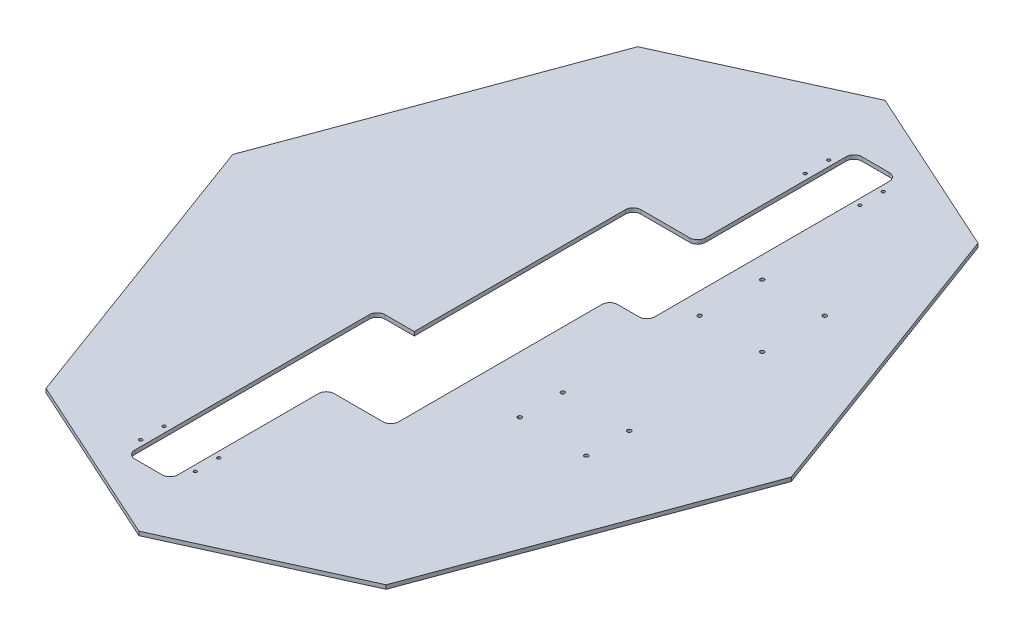
SolidWorks part; units mm, degrees
material "6061-T6 (SS)"
ref_plane "Front Plane" through (0, 0, 0) normal (0, 0, 1) x (1, 0, 0)
ref_plane "Top Plane" through (0, 0, 0) normal (0, 1, 0) x (1, 0, 0)
ref_plane "Right Plane" through (0, 0, 0) normal (1, 0, 0) x (0, 0, -1)
sketch "Sketch1" plane through (0, 0, 0) normal (0, 1, 0) x (1, 0, 0)
  line L0 (0, -483.0506) -> (0, 483.0506) construction
  line L1 (-276.37, 480.7072) -> (-453.8156, 0)
  line L2 (-276.37, -480.7072) -> (-453.8156, 0)
  line L3 (0, -606.1134) -> (-276.37, -480.7072)
  line L4 (276.37, -480.7072) -> (0, -606.1134)
  line L5 (278.8894, 0) -> (-278.8894, 0) construction
  line L6 (276.37, -480.7072) -> (453.8156, 0)
  line L7 (453.8156, 0) -> (276.37, 480.7072)
  line L8 (276.37, 480.7072) -> (0, 606.1134)
  line L9 (-276.37, 480.7072) -> (0, 606.1134)
  line L23 (-278.8894, -483.0506) -> (-457.2, 0) construction
  line L24 (0, -609.6) -> (-278.8894, -483.0506) construction
  line L25 (278.8894, -483.0506) -> (0, -609.6) construction
  line L26 (278.8894, -483.0506) -> (457.2, 0) construction
  line L27 (457.2, 0) -> (278.8894, 483.0506) construction
  line L28 (278.8894, 483.0506) -> (0, 609.6) construction
  line L29 (-278.8894, 483.0506) -> (0, 609.6) construction
  line L30 (-278.8894, 483.0506) -> (-457.2, 0) construction
  line L39 (-278.8894, -483.0506) -> (278.8894, -483.0506) construction
  line L40 (-278.8894, -483.0506) -> (-278.8894, 483.0506) construction
  line L41 (-278.8894, 483.0506) -> (278.8894, 483.0506) construction
  line L42 (278.8894, -483.0506) -> (278.8894, 483.0506) construction
  line L43 (-278.8894, -483.0506) -> (278.8894, 483.0506) construction
  line L44 (-278.8894, 483.0506) -> (278.8894, -483.0506) construction
  ellipse E0 centre (0, 0) end of major axis (0, 609.6) minor radius 457.2 construction
  point P50 (0, 0)
  dimension "D1" = 3.175
  dimension "D3" = 30
  dimension "D8" = 609.6
  dimension "D9" = 457.2
extrude "Boss-Extrude1" add sketch "Sketch1" along normal mid plane 6.35
sketch "Sketch2" plane through (0, 0, 0) normal (0, 1, 0) x (1, 0, 0)
  line L0 (82.55, 457.2) -> (38.1, 457.2) construction
  line L1 (82.55, -457.2) -> (-82.55, -457.2) construction
  line L2 (82.55, -457.2) -> (82.55, 457.2) construction
  line L3 (82.55, 457.2) -> (-82.55, 457.2) construction
  line L4 (-82.55, -457.2) -> (-82.55, 457.2) construction
  line L5 (82.55, -457.2) -> (-82.55, 457.2) construction
  line L6 (82.55, 457.2) -> (-82.55, -457.2) construction
  line L7 (47.625, 101.6) -> (117.475, 101.6)
  line L8 (47.625, 101.6) -> (47.625, 508)
  line L9 (47.625, 508) -> (117.475, 508)
  line L10 (117.475, 101.6) -> (117.475, 508)
  line L11 (82.55, 508) -> (82.55, 457.2) construction
  line L12 (-82.55, -457.2) -> (-82.55, -508) construction
  line L13 (-47.625, -508) -> (-117.475, -508)
  line L14 (-47.625, -508) -> (-47.625, -101.6)
  line L15 (-47.625, -101.6) -> (-117.475, -101.6)
  line L16 (-117.475, -508) -> (-117.475, -101.6)
  line L18 (-57.15, -254) -> (57.15, -254)
  line L19 (38.1, 438.15) -> (38.1, 476.25) construction
  line L20 (-82.55, -457.2) -> (-127, -457.2) construction
  line L21 (-127, -476.25) -> (-127, -438.15) construction
  line L22 (-57.15, -254) -> (-57.15, 254)
  line L23 (-57.15, 254) -> (57.15, 254)
  line L24 (57.15, -254) -> (57.15, 254)
  line L25 (-57.15, -254) -> (57.15, 254) construction
  line L26 (-57.15, 254) -> (57.15, -254) construction
  circle A0 centre (38.1, 476.25) radius 2.54
  circle A1 centre (38.1, 438.15) radius 2.54
  circle A2 centre (127, 438.15) radius 2.54
  circle A3 centre (127, 476.25) radius 2.54
  circle A4 centre (-127, -438.15) radius 2.54
  circle A5 centre (-127, -476.25) radius 2.54
  circle A6 centre (-38.1, -476.25) radius 2.54
  circle A7 centre (-38.1, -438.15) radius 2.54
  point P0 (0, 0)
  point P17 (85.725, 457.2)
  point P20 (38.1, 457.2)
  point P29 (-127, -457.2)
  point P36 (0, 0)
  dimension "D7" = 5.08
  dimension "D1" = 82.55
  dimension "D2" = 914.4
  dimension "D3" = 69.85
  dimension "D4" = 406.4
  dimension "D5" = 44.45
  dimension "D6" = 38.1
  dimension "D8" = 50.8
  dimension "D9" = 50.8
  dimension "D10" = 114.3
  dimension "D11" = 508
extrude "Cut-Extrude1" cut sketch "Sketch2" against normal through all both and the other way through all contours L18 L22 L15 L16 L13 L14 | L22 L23 L24 L18 | L10 L9 L8 L7 | A3 | A2 | A1 | A0 | A7 | A6 | A4 | A5 region at (-84.1755, 0, 311.6443)
fillet "Fillet1" radius 12.7 11 edges at (-117.475, 0, 508) (47.625, 0, -508) (117.475, 0, -508) (117.475, 0, -101.6) (-117.475, 0, 101.6) (-47.625, 0, 508) (-47.625, 0, 254) (57.15, 0, 254) (57.15, 0, -101.6) (-57.15, 0, -254) (47.625, 0, -254)
sketch "Sketch4" plane through (0, 3.175, 0) normal (0, 1, 0) x (1, 0, 0)
  line L1 (149.225, -66.675) -> (257.175, -66.675) construction
  line L2 (149.225, -66.675) -> (149.225, -136.525) construction
  line L3 (149.225, -136.525) -> (257.175, -136.525) construction
  line L4 (257.175, -66.675) -> (257.175, -136.525) construction
  line L5 (149.225, -66.675) -> (257.175, -136.525) construction
  line L6 (149.225, -136.525) -> (257.175, -66.675) construction
  line L7 (152.4, 254) -> (254, 254) construction
  line L8 (152.4, 254) -> (152.4, 152.4) construction
  line L9 (152.4, 152.4) -> (254, 152.4) construction
  line L10 (254, 254) -> (254, 152.4) construction
  line L11 (152.4, 254) -> (254, 152.4) construction
  line L12 (152.4, 152.4) -> (254, 254) construction
  circle A0 centre (257.175, -66.675) radius 3.175
  circle A1 centre (149.225, -66.675) radius 3.175
  circle A2 centre (149.225, -136.525) radius 3.175
  circle A3 centre (257.175, -136.525) radius 3.175
  circle A4 centre (152.4, 254) radius 3.175
  circle A5 centre (254, 254) radius 3.175
  circle A6 centre (254, 152.4) radius 3.175
  circle A7 centre (152.4, 152.4) radius 3.175
  point P0 (203.2, -101.6)
  point P9 (203.2, 203.2)
  dimension "D1" = 6.35
  dimension "D8" = 6.35
  dimension "D2" = 107.95
  dimension "D3" = 69.85
  dimension "D4" = 101.6
  dimension "D5" = 203.2
  dimension "D6" = 101.6
  dimension "D7" = 304.8
extrude "Cut-Extrude3" cut sketch "Sketch4" against normal up to next
